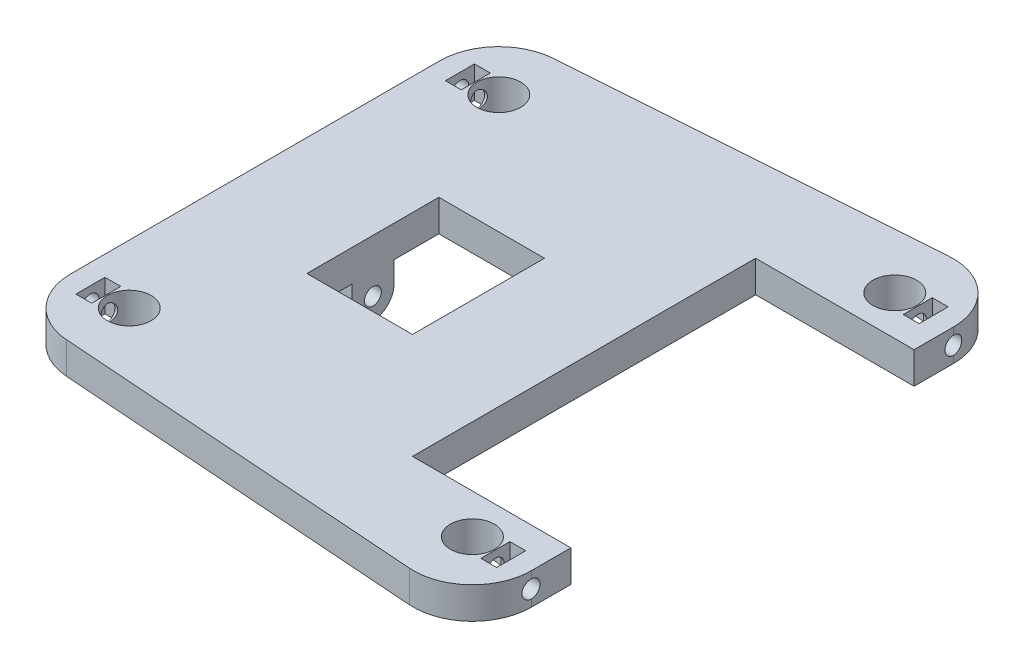
SolidWorks part; units mm, degrees
material "ABS"
ref_plane "Plano frontal" through (0, 0, 0) normal (0, 0, 1) x (1, 0, 0)
ref_plane "Plano superior" through (0, 0, 0) normal (0, 1, 0) x (1, 0, 0)
ref_plane "Plano direito" through (0, 0, 0) normal (1, 0, 0) x (0, 0, -1)
sketch "Esboço2" plane through (0, 0, 0) normal (0, 1, 0) x (1, 0, 0)
  line L0 (0, 0) -> (24.9005, 0) construction
  line L1 (-0.7944, 46.1217) -> (69.2056, 51.1217)
  line L2 (-11.15, 35) -> (-11.15, -35)
  line L3 (81.15, 40) -> (81.15, 32.5)
  line L4 (-0.7944, -46.1217) -> (69.2056, -51.1217)
  line L5 (74.35, -37.25) -> (77.35, -42.75) construction
  line L6 (-4.35, 37.75) -> (-7.35, 37.75)
  line L7 (-4.35, 37.75) -> (-4.35, 32.25)
  line L8 (-4.35, 32.25) -> (-7.35, 32.25)
  line L9 (-7.35, 37.75) -> (-7.35, 32.25)
  line L10 (-4.35, 37.75) -> (-7.35, 32.25) construction
  line L11 (-4.35, 32.25) -> (-7.35, 37.75) construction
  line L12 (74.35, 42.75) -> (77.35, 42.75)
  line L13 (74.35, 42.75) -> (74.35, 37.25)
  line L14 (74.35, 37.25) -> (77.35, 37.25)
  line L15 (77.35, 42.75) -> (77.35, 37.25)
  line L16 (74.35, 42.75) -> (77.35, 37.25) construction
  line L17 (74.35, 37.25) -> (77.35, 42.75) construction
  line L18 (74.35, -42.75) -> (77.35, -37.25) construction
  line L19 (77.35, -42.75) -> (77.35, -37.25)
  line L20 (74.35, -37.25) -> (77.35, -37.25)
  line L21 (74.35, -42.75) -> (74.35, -37.25)
  line L22 (74.35, -42.75) -> (77.35, -42.75)
  line L23 (-4.35, -32.25) -> (-7.35, -37.75) construction
  line L24 (-4.35, -37.75) -> (-7.35, -32.25) construction
  line L25 (-7.35, -37.75) -> (-7.35, -32.25)
  line L26 (-4.35, -32.25) -> (-7.35, -32.25)
  line L27 (-4.35, -37.75) -> (-4.35, -32.25)
  line L28 (-4.35, -37.75) -> (-7.35, -37.75)
  line L29 (20, 35) -> (20, -35) construction
  line L30 (81.15, -32.5) -> (81.15, -40)
  line L31 (11.15, -12.5) -> (31.15, -12.5)
  line L32 (11.15, -12.5) -> (11.15, 12.5)
  line L33 (11.15, 12.5) -> (31.15, 12.5)
  line L34 (31.15, -12.5) -> (31.15, 12.5)
  line L35 (11.15, -12.5) -> (31.15, 12.5) construction
  line L36 (11.15, 12.5) -> (31.15, -12.5) construction
  line L37 (51.15, 32.5) -> (81.15, 32.5)
  line L38 (51.15, 32.5) -> (51.15, -32.5)
  line L39 (51.15, -32.5) -> (81.15, -32.5)
  line L41 (51.15, 32.5) -> (81.15, -32.5) construction
  line L42 (51.15, -32.5) -> (81.15, 32.5) construction
  circle A0 centre (0, 35) radius 4.15
  arc A1 (81.15, -40) -> (69.2056, -51.1217) centre (70, -40) cw
  circle A2 centre (70, 40) radius 4.15
  arc A3 (-0.7944, -46.1217) -> (-11.15, -35) centre (0, -35) cw
  arc A4 (-0.7944, 46.1217) -> (-11.15, 35) centre (0, 35) ccw
  arc A5 (81.15, 40) -> (69.2056, 51.1217) centre (70, 40) ccw
  circle A6 centre (70, -40) radius 4.15
  circle A7 centre (0, -35) radius 4.15
  point P0 (21.15, 0)
  point P5 (75.85, 40)
  point P16 (-5.85, 35)
  point P18 (-11.15, 0)
  point P25 (79.1, 0)
  point P35 (75.85, -40)
  point P40 (-5.85, -35)
  point P47 (66.15, 0)
  dimension "D1" = 8.3
  dimension "D2" = 8.3
  dimension "D5" = 70
  dimension "D6" = 7
  dimension "D7" = 7
  dimension "D4" = 70
  dimension "D8" = 5.5
  dimension "D9" = 3
  dimension "D10" = 0.2
  dimension "D11" = 0.2
  dimension "D3" = 80
  dimension "D15" = 20
  dimension "D12" = 20
  dimension "D13" = 50
  dimension "D14" = 25
  dimension "D16" = 65
  dimension "D17" = 30
extrude "Ressalto-extrusão1" add sketch "Esboço2" along normal blind 6
sketch "Esboço4" plane through (11.15, 0, 0) normal (1, 0, 0) x (0, 0, -1)
  line L0 (-4, -4) -> (-4, 0)
  line L2 (-4, 0) -> (4, 0)
  line L3 (4, 0) -> (4, -4)
  line L4 (-32.5, 0) -> (32.5, 0) construction
  circle A0 centre (0, -4) radius 1.6
  arc A1 (-4, -4) -> (4, -4) centre (0, -4) ccw
  dimension "D1" = 3.2
  dimension "D3" = 4
  dimension "D2" = 4
extrude "Ressalto-extrusão2" add sketch "Esboço4" against normal blind 4
extrude "Ressalto-extrusão3" add sketch "Esboço4<2>" along normal blind 4 from vertex starting at point (31.15, 6, 12.5)
sketch "Esboço4<2>" plane through (11.15, 0, 0) normal (1, 0, 0) x (0, 0, -1) same geometry as "Esboço4"
sketch "Esboço5" plane through (0, 0, 0) normal (0, -1, 0) x (1, 0, 0)
  line L0 (0, 0) -> (95.7172, 0) construction
  line L1 (70, -32.5) -> (70, -34.5)
  line L2 (51.15, -32.5) -> (81.15, -32.5) construction
  line L3 (70, -34.5) -> (50.7687, -37.5)
  line L4 (50.7687, -37.5) -> (47.4264, -36.9872)
  line L5 (47.4264, -36.9872) -> (48.1847, -32.045)
  line L6 (48.1847, -32.045) -> (51.15, -32.5)
  line L7 (-11.15, -22.9415) -> (-7.1963, -23.5481)
  line L8 (-11.15, -35) -> (-11.15, 35) construction
  line L9 (-7.1963, -23.5481) -> (-7.9545, -28.4903)
  line L10 (-7.9545, -28.4903) -> (-11.15, -28)
  line L11 (-11.15, -28) -> (-11.15, -22.9415)
  line L12 (-7.5754, -26.0192) -> (47.8056, -34.5161) construction
  line L13 (-7.5754, 26.0192) -> (47.8056, 34.5161) construction
  line L14 (-11.15, 28) -> (-11.15, 22.9415)
  line L15 (-7.9545, 28.4903) -> (-11.15, 28)
  line L16 (-7.1963, 23.5481) -> (-7.9545, 28.4903)
  line L17 (-11.15, 22.9415) -> (-7.1963, 23.5481)
  line L18 (48.1847, 32.045) -> (51.15, 32.5)
  line L19 (47.4264, 36.9872) -> (48.1847, 32.045)
  line L20 (50.7687, 37.5) -> (47.4264, 36.9872)
  line L21 (70, 34.5) -> (50.7687, 37.5)
  line L22 (70, 32.5) -> (70, 34.5)
  line L23 (51.15, -32.5) -> (70, -32.5)
  line L24 (51.15, 32.5) -> (70, 32.5)
  circle A0 centre (0, -35) radius 4.15 construction
  point P16 (70, -40)
  point P43 (70, 40)
  dimension "D1" = 2
  dimension "D2" = 5
  dimension "D3" = 5
  dimension "D4" = 5
  dimension "D5" = 3
  dimension "D6" = 7
  dimension "D7" = 4
extrude "Ressalto-extrusão4" [suppressed] add sketch "Esboço5" along normal blind 4
sketch "Esboço6" [suppressed] plane through (0, 0, 0) normal (0, -1, 0) x (1, 0, 0)
  line L0 (-11.15, 25.4707) -> (47.8056, 34.5161) construction
  line L1 (-11.15, 28) -> (-11.15, 22.9415) construction
  line L2 (47.4264, 36.9872) -> (48.1847, 32.045) construction
  line L3 (0, 0) -> (68.3855, 0) construction
  line L5 (-7.1963, 23.5481) -> (-7.9545, 28.4903) construction
  line L6 (47.8056, 34.5161) -> (70, 34.5) construction
  line L7 (-11.0742, 24.9765) -> (47.8435, 34.0161)
  line L8 (47.8435, 34.0161) -> (69.9996, 34)
  line L9 (-11.2258, 25.965) -> (47.7676, 35.0162)
  line L10 (47.7676, 35.0162) -> (70.0004, 35)
  line L11 (47.8056, -34.5161) -> (70, -34.5) construction
  line L12 (-11.15, -25.4707) -> (47.8056, -34.5161) construction
  line L13 (47.7676, -35.0162) -> (70.0004, -35)
  line L14 (-11.2258, -25.965) -> (47.7676, -35.0162)
  line L15 (47.8435, -34.0161) -> (69.9996, -34)
  line L16 (-11.0742, -24.9765) -> (47.8435, -34.0161)
  arc A0 (-11.0742, 24.9765) -> (-11.2258, 25.965) centre (-11.15, 25.4707) cw
  arc A1 (69.9996, 34) -> (70.0004, 35) centre (70, 34.5) ccw
  arc A2 (69.9996, -34) -> (70.0004, -35) centre (70, -34.5) cw
  arc A3 (-11.0742, -24.9765) -> (-11.2258, -25.965) centre (-11.15, -25.4707) ccw
  point P11 (-7.5754, 26.0192)
  point P25 (-7.5754, -26.0192)
  dimension "D1" = 0.5
  dimension "D2" = 0.5
extrude "Corte-extrusão1" [suppressed] cut sketch "Esboço6" along normal blind 1
fillet "Filete1" [suppressed] radius 0.5
sketch "Esboço7" plane through (74.35, 0, 0) normal (1, 0, 0) x (0, 0, -1)
  line L1 (37.25, 6) -> (37.25, 0) construction
  line L2 (42.75, 6) -> (37.25, 6) construction
  circle A0 centre (40, 3) radius 1.65
  point P2 (37.25, 3)
  point P5 (40, 6)
  dimension "D1" = 3.3
extrude "Corte-extrusão2" cut sketch "Esboço7" against normal blind 1 and the other way through all
sketch "Esboço8" plane through (-4.35, 0, 0) normal (-1, 0, 0) x (0, 0, 1)
  line L0 (32.25, 6) -> (32.25, 0) construction
  line L1 (37.75, 6) -> (32.25, 6) construction
  circle A0 centre (35, 3) radius 1.65
  point P2 (35, 6)
  point P5 (32.25, 3)
  dimension "D1" = 3.3
extrude "Corte-extrusão3" cut sketch "Esboço8" against normal blind 1 and the other way through all
mirror "Espelhar1" about plane through (0, 0, 0) normal (0, 0, 1) of "Corte-extrusão3", "Corte-extrusão2"
equation "\"D7@Esboço2\"=\"D6@Esboço2\""
